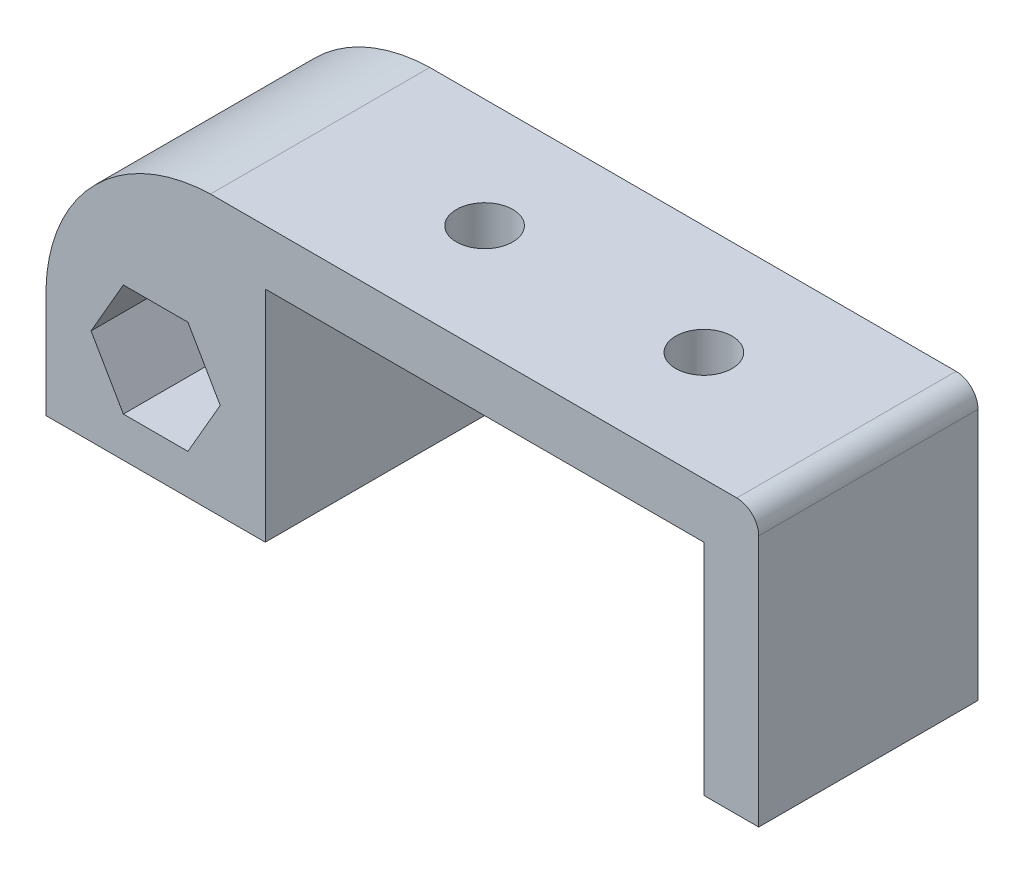
SolidWorks part; units mm, degrees
material "Printed PLA Orthotropic"
ref_plane "Front Plane" through (0, 0, 0) normal (0, 0, 1) x (1, 0, 0)
ref_plane "Top Plane" through (0, 0, 0) normal (0, 1, 0) x (1, 0, 0)
ref_plane "Right Plane" through (0, 0, 0) normal (1, 0, 0) x (0, 0, -1)
sketch "Sketch1" plane through (0, 0, 0) normal (0, 0, 1) x (1, 0, 0)
  line L0 (50.8, 0) -> (57.15, 0)
  line L2 (0, 0) -> (0, 25.4)
  line L3 (0, 25.4) -> (50.8, 25.4)
  line L4 (50.8, 0) -> (50.8, 25.4)
  line L5 (57.15, 0) -> (57.15, 29.21)
  line L6 (54.61, 31.75) -> (-6.35, 31.75)
  line L7 (0, 0) -> (-25.4, 0)
  line L8 (-8.9605, 4.6355) -> (-5.221, 11.1125)
  line L9 (-5.221, 11.1125) -> (-8.9605, 17.5895)
  line L10 (-8.9605, 17.5895) -> (-16.4395, 17.5895)
  line L11 (-16.4395, 17.5895) -> (-20.179, 11.1125)
  line L12 (-20.179, 11.1125) -> (-16.4395, 4.6355)
  line L13 (-16.4395, 4.6355) -> (-8.9605, 4.6355)
  line L14 (-25.4, 0) -> (-25.4, 12.7)
  arc A0 (57.15, 29.21) -> (54.61, 31.75) centre (54.61, 29.21) ccw
  circle A1 centre (-12.7, 11.1125) radius 6.477 construction
  arc A2 (-25.4, 12.7) -> (-6.35, 31.75) centre (-5.849, 12.199) cw
  point P10 (57.15, 31.75)
  point P21 (0, 0)
  dimension "D6" = 2.54
  dimension "D8" = 12.7
  dimension "D10" = 11.1125
  dimension "D1" = 50.8
  dimension "D2" = 25.4
  dimension "D3" = 63.5
  dimension "D4" = 31.75
  dimension "D5" = 6.35
  dimension "D7" = 12.954
  dimension "D9" = 25.4
  dimension "D11" = 12.7
extrude "Boss-Extrude2" add sketch "Sketch1" along normal blind 25.4
sketch "Sketch2" plane through (0, 31.75, 0) normal (0, 1, 0) x (1, 0, 0)
  line L0 (54.61, 0) -> (-6.35, 0) construction
  line L1 (25.4, 0) -> (25.4, -25.4) construction
  circle A0 centre (12.7, -12.7) radius 3.2639
  circle A1 centre (38.1, -12.7) radius 3.2639
  point P4 (0, 0)
  dimension "D1" = 12.7
  dimension "D3" = 6.5278
  dimension "D2" = 12.7
  dimension "D4" = 12.7
extrude "Cut-Extrude1" cut sketch "Sketch2" against normal through all
equation "\"x\"=0.1"
